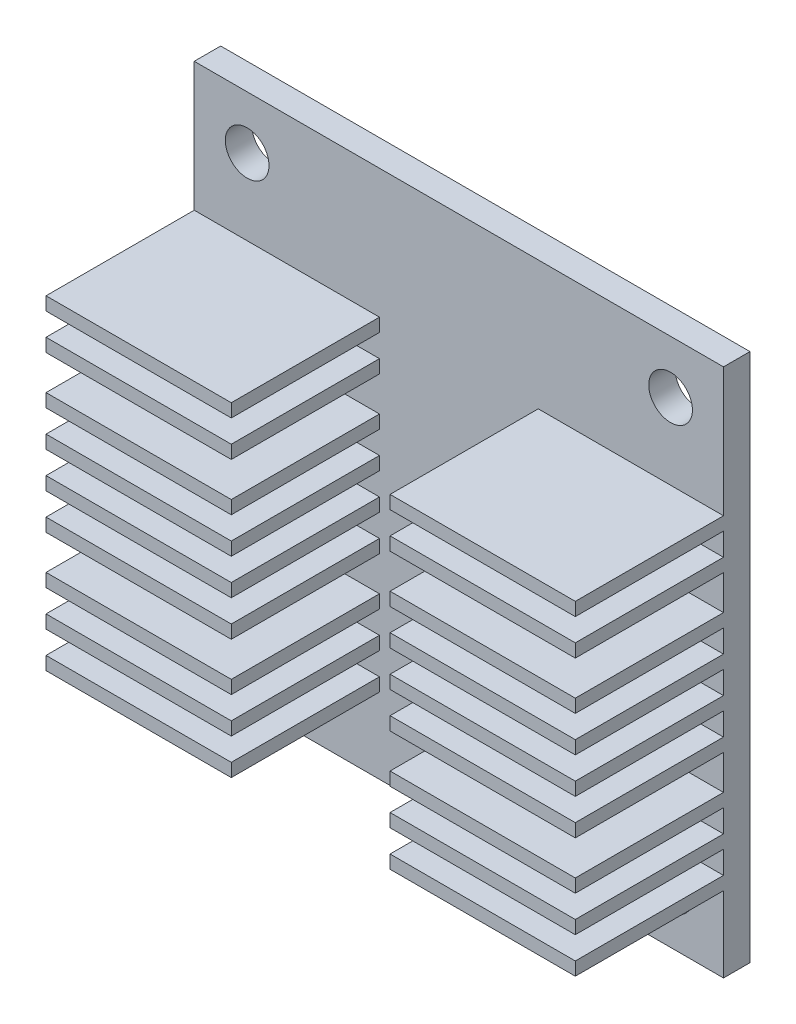
SolidWorks part; units mm, degrees
ref_plane "Front Plane" through (0, 0, 0) normal (0, 0, 1) x (1, 0, 0)
ref_plane "Top Plane" through (0, 0, 0) normal (0, 1, 0) x (1, 0, 0)
ref_plane "Right Plane" through (0, 0, 0) normal (1, 0, 0) x (0, 0, -1)
sketch "Sketch1" plane through (0, 0, 0) normal (0, 0, 1) x (1, 0, 0)
  line L0 (41, 4.4837) -> (27, 4.4837)
  line L1 (41, 2.4837) -> (1, 2.4837)
  line L2 (41, 2.4837) -> (41, 42.4837)
  line L3 (41, 42.4837) -> (1, 42.4837)
  line L4 (1, 2.4837) -> (1, 42.4837)
  line L5 (21, 40.4837) -> (21, 4.4837) construction
  line L6 (41, 21.7785) -> (27, 21.7785) construction
  line L7 (41, 4.4837) -> (41, 40.4837)
  line L8 (27, 4.4837) -> (27, 40.4837)
  line L9 (15, 4.4837) -> (15, 40.4837)
  line L10 (1, 4.4837) -> (1, 40.4837)
  line L11 (25, 4.4837) -> (25, 40.4837)
  line L12 (17, 4.4837) -> (17, 40.4837)
  line L13 (41, 40.4837) -> (27, 40.4837)
  line L14 (41, 5.4837) -> (27, 5.4837)
  line L15 (41, 6.389) -> (27, 6.389)
  line L16 (41, 7.2943) -> (27, 7.2943)
  line L17 (41, 8.1995) -> (27, 8.1995)
  line L18 (41, 9.1048) -> (27, 9.1048)
  line L19 (41, 10.01) -> (27, 10.01)
  line L20 (41, 10.9153) -> (27, 10.9153)
  line L21 (41, 11.8206) -> (27, 11.8206)
  line L22 (41, 12.7258) -> (27, 12.7258)
  line L23 (41, 13.6311) -> (27, 13.6311)
  line L24 (41, 14.5364) -> (27, 14.5364)
  line L25 (41, 15.4416) -> (27, 15.4416)
  line L26 (41, 16.3469) -> (27, 16.3469)
  line L27 (41, 17.2522) -> (27, 17.2522)
  line L28 (41, 18.1574) -> (27, 18.1574)
  line L29 (41, 19.0627) -> (27, 19.0627)
  line L30 (41, 19.9679) -> (27, 19.9679)
  line L31 (41, 20.8732) -> (27, 20.8732)
  line L32 (41, 21.7785) -> (27, 21.7785)
  line L33 (41, 22.6837) -> (27, 22.6837)
  line L34 (41, 23.589) -> (27, 23.589)
  line L35 (41, 24.4943) -> (27, 24.4943)
  line L36 (41, 25.3995) -> (27, 25.3995)
  line L37 (41, 26.3048) -> (27, 26.3048)
  line L38 (41, 27.21) -> (27, 27.21)
  line L39 (41, 28.1153) -> (27, 28.1153)
  line L40 (41, 29.0206) -> (27, 29.0206)
  line L41 (41, 29.9258) -> (27, 29.9258)
  line L42 (41, 30.8311) -> (27, 30.8311)
  line L43 (41, 31.7364) -> (27, 31.7364)
  line L44 (41, 32.6416) -> (27, 32.6416)
  line L45 (41, 33.5469) -> (27, 33.5469)
  line L46 (41, 34.4522) -> (27, 34.4522)
  line L47 (41, 35.3574) -> (27, 35.3574)
  line L48 (41, 36.2627) -> (27, 36.2627)
  line L49 (41, 37.1679) -> (27, 37.1679)
  line L50 (41, 38.0732) -> (27, 38.0732)
  line L51 (46.6374, 3.6837) -> (46.6374, 4.6837) construction
  line L52 (45.6374, 5.4837) -> (-11.288, 5.4837) construction
  line L53 (45.6374, 4.4837) -> (-11.288, 4.4837) construction
  line L54 (25, 4.4837) -> (17, 4.4837)
  line L55 (25, 5.4837) -> (17, 5.4837)
  line L56 (25, 6.389) -> (17, 6.389)
  line L57 (25, 7.2943) -> (17, 7.2943)
  line L58 (25, 8.1995) -> (17, 8.1995)
  line L59 (25, 9.1048) -> (17, 9.1048)
  line L60 (25, 10.01) -> (17, 10.01)
  line L61 (25, 10.9153) -> (17, 10.9153)
  line L62 (25, 11.8206) -> (17, 11.8206)
  line L63 (25, 12.7258) -> (17, 12.7258)
  line L64 (25, 13.6311) -> (17, 13.6311)
  line L65 (25, 14.5364) -> (17, 14.5364)
  line L66 (25, 15.4416) -> (17, 15.4416)
  line L67 (25, 16.3469) -> (17, 16.3469)
  line L68 (25, 17.2522) -> (17, 17.2522)
  line L69 (25, 18.1574) -> (17, 18.1574)
  line L70 (25, 19.0627) -> (17, 19.0627)
  line L71 (25, 19.9679) -> (17, 19.9679)
  line L72 (25, 20.8732) -> (17, 20.8732)
  line L73 (25, 21.7785) -> (17, 21.7785) construction
  line L74 (25, 21.7785) -> (17, 21.7785)
  line L75 (25, 22.6837) -> (17, 22.6837)
  line L76 (25, 23.589) -> (17, 23.589)
  line L77 (25, 24.4943) -> (17, 24.4943)
  line L78 (25, 25.3995) -> (17, 25.3995)
  line L79 (25, 26.3048) -> (17, 26.3048)
  line L80 (25, 27.21) -> (17, 27.21)
  line L81 (25, 28.1153) -> (17, 28.1153)
  line L82 (25, 29.0206) -> (17, 29.0206)
  line L83 (25, 29.9258) -> (17, 29.9258)
  line L84 (25, 30.8311) -> (17, 30.8311)
  line L85 (25, 31.7364) -> (17, 31.7364)
  line L86 (25, 32.6416) -> (17, 32.6416)
  line L87 (25, 33.5469) -> (17, 33.5469)
  line L88 (25, 34.4522) -> (17, 34.4522)
  line L89 (25, 35.3574) -> (17, 35.3574)
  line L90 (25, 36.2627) -> (17, 36.2627)
  line L91 (25, 37.1679) -> (17, 37.1679)
  line L92 (25, 38.0732) -> (17, 38.0732)
  line L93 (25, 40.4837) -> (17, 40.4837)
  line L94 (15, 4.4837) -> (1, 4.4837)
  line L95 (15, 5.4837) -> (1, 5.4837)
  line L96 (15, 6.389) -> (1, 6.389)
  line L97 (15, 7.2943) -> (1, 7.2943)
  line L98 (15, 8.1995) -> (1, 8.1995)
  line L99 (15, 9.1048) -> (1, 9.1048)
  line L100 (15, 10.01) -> (1, 10.01)
  line L101 (15, 10.9153) -> (1, 10.9153)
  line L102 (15, 11.8206) -> (1, 11.8206)
  line L103 (15, 12.7258) -> (1, 12.7258)
  line L104 (15, 13.6311) -> (1, 13.6311)
  line L105 (15, 14.5364) -> (1, 14.5364)
  line L106 (15, 15.4416) -> (1, 15.4416)
  line L107 (15, 16.3469) -> (1, 16.3469)
  line L108 (15, 17.2522) -> (1, 17.2522)
  line L109 (15, 18.1574) -> (1, 18.1574)
  line L110 (15, 19.0627) -> (1, 19.0627)
  line L111 (15, 19.9679) -> (1, 19.9679)
  line L112 (15, 20.8732) -> (1, 20.8732)
  line L113 (15, 21.7785) -> (1, 21.7785) construction
  line L114 (15, 21.7785) -> (1, 21.7785)
  line L115 (15, 22.6837) -> (1, 22.6837)
  line L116 (15, 23.589) -> (1, 23.589)
  line L117 (15, 24.4943) -> (1, 24.4943)
  line L118 (15, 25.3995) -> (1, 25.3995)
  line L119 (15, 26.3048) -> (1, 26.3048)
  line L120 (15, 27.21) -> (1, 27.21)
  line L121 (15, 28.1153) -> (1, 28.1153)
  line L122 (15, 29.0206) -> (1, 29.0206)
  line L123 (15, 29.9258) -> (1, 29.9258)
  line L124 (15, 30.8311) -> (1, 30.8311)
  line L125 (15, 31.7364) -> (1, 31.7364)
  line L126 (15, 32.6416) -> (1, 32.6416)
  line L127 (15, 33.5469) -> (1, 33.5469)
  line L128 (15, 34.4522) -> (1, 34.4522)
  line L129 (15, 35.3574) -> (1, 35.3574)
  line L130 (15, 36.2627) -> (1, 36.2627)
  line L131 (15, 37.1679) -> (1, 37.1679)
  line L132 (15, 38.0732) -> (1, 38.0732)
  line L133 (15, 40.4837) -> (1, 40.4837)
  point P48 (21, 21.7785)
  dimension "D1" = 2
  dimension "D2" = 2
  dimension "D3" = 0
  dimension "D4" = 0
  dimension "D5" = 2
  dimension "D6" = 2
  dimension "D7" = 14
  dimension "D8" = 14
  dimension "D10" = 1
  dimension "D9" = 1
extrude "Boss-Extrude1" add sketch "Sketch1" along normal blind 2 contours L1 L4 L3 L2
extrude "Extrude-Thin1" add sketch "Sketch1<3>" along normal blind 11.2 from surface thin contours L17 | L20 | L98 | L101 | L23 | L104 | L36 | L33 | L30 | L27 | L108 | L111 | L115 | L118 | L40 | L122 | L43 | L125 starting at face at (21, 22.4837, 2) thin type one direction wall 1
sketch "Sketch1<3>" plane through (0, 0, 0) normal (0, 0, 1) x (1, 0, 0) same geometry as "Sketch1"
sketch "Sketch3" plane through (0, 0, 0) normal (0, 0, -1) x (-1, 0, 0)
  line L0 (-41, 2.4837) -> (-41, 42.4837) construction
  circle A0 centre (-37, 6.4837) radius 1.65
  dimension "D1" = 3.3
  dimension "D2" = 4
extrude "Cut-Extrude1" cut sketch "Sketch3" against normal up to surface (13.2 mm away) from surface contours A0 up to face at (34, 8.6995, 13.2) starting at face at (21, 22.4837, 0)
pattern_linear "LPattern1" count 2 spacing 32 along (-1, 0, 0) count 2 spacing 32 along (0, 1, 0) of "Cut-Extrude1"
